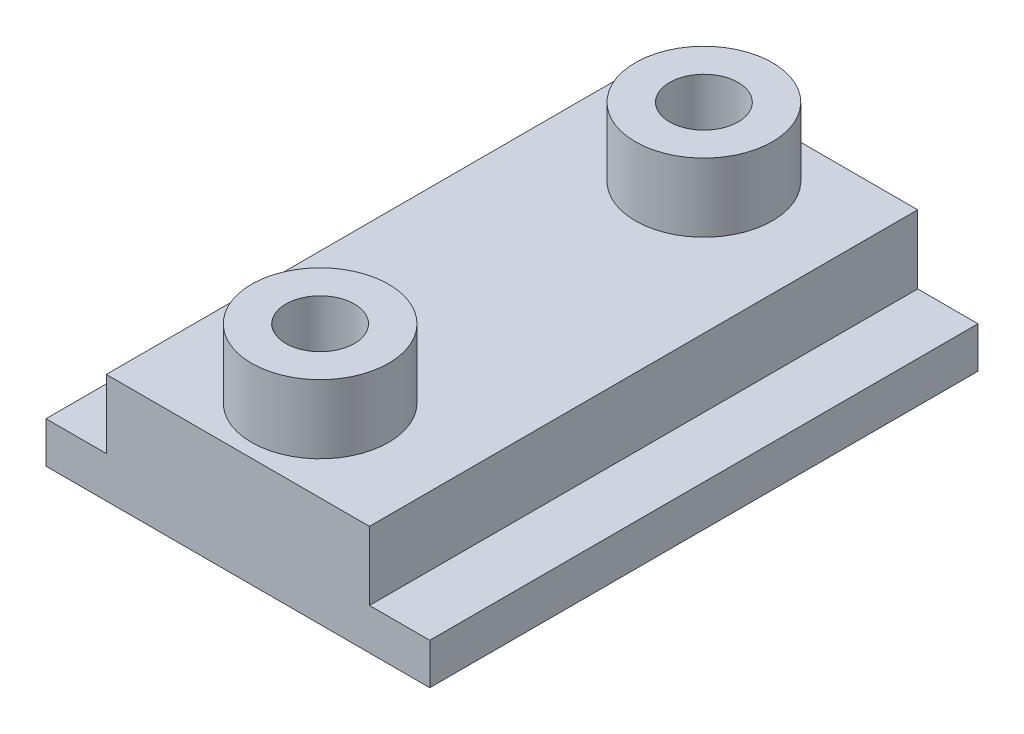
SolidWorks part; units mm, degrees
ref_plane "Ebene vorne" through (0, 0, 0) normal (0, 0, 1) x (1, 0, 0)
ref_plane "Ebene oben" through (0, 0, 0) normal (0, 1, 0) x (1, 0, 0)
ref_plane "Ebene rechts" through (0, 0, 0) normal (1, 0, 0) x (0, 0, -1)
sketch "Skizze1" plane through (0, 0, 0) normal (0, 0, 1) x (1, 0, 0)
  line L0 (-7, 0) -> (7, 0)
  line L1 (7, 0) -> (7, 1.5)
  line L2 (7, 1.5) -> (4.8, 1.5)
  line L3 (4.8, 1.5) -> (4.8, 4)
  line L4 (4.8, 4) -> (-4.8, 4)
  line L5 (-4.8, 4) -> (-4.8, 1.5)
  line L6 (-4.8, 1.5) -> (-7, 1.5)
  line L7 (-7, 1.5) -> (-7, 0)
  dimension "D1" = 1.5
  dimension "D2" = 14
  dimension "D3" = 9.6
  dimension "D4" = 4
extrude "Aufsatz-Linear austragen1" add sketch "Skizze1" along normal blind 10 and the other way blind 10
sketch "Skizze2" plane through (0, 4, 0) normal (0, 1, 0) x (1, 0, 0)
  circle A0 centre (0, 7) radius 2.5
  circle A1 centre (0, -7) radius 2.5
  dimension "D3" = 5
  dimension "D1" = 14
  dimension "D2" = 7
extrude "Aufsatz-Linear austragen2" add sketch "Skizze2" along normal blind 2.5
hole_wizard "M3 Gewindebohrung1" positions "Skizze4" profile "Skizze3" tap size "M3" standard "DIN" end condition through all
sketch "Skizze4" plane through (0, 6.5, 0) normal (0, 1, 0) x (1, 0, 0)
  point P0 (0, -7)
  point P2 (0, 7)
sketch "Skizze3" plane through (0, 6.5, 7) normal (1, 0, 0) x (0, 0, 1)
  line L0 (0, 0) -> (0, 6.5)
  line L1 (0, 6.5) -> (1.25, 6.5)
  line L2 (1.25, 6.5) -> (1.25, 0)
  line L5 (1.25, 0) -> (0, 0)
  line L11 (0, -6.35) -> (0, 107.95) construction
  dimension "Bohrerdurchmesser" = 2.5
  dimension "Bohrungstiefe" = 6.5
cosmetic thread "Bohrungsgewinde1"
cosmetic thread "Bohrungsgewinde2"
